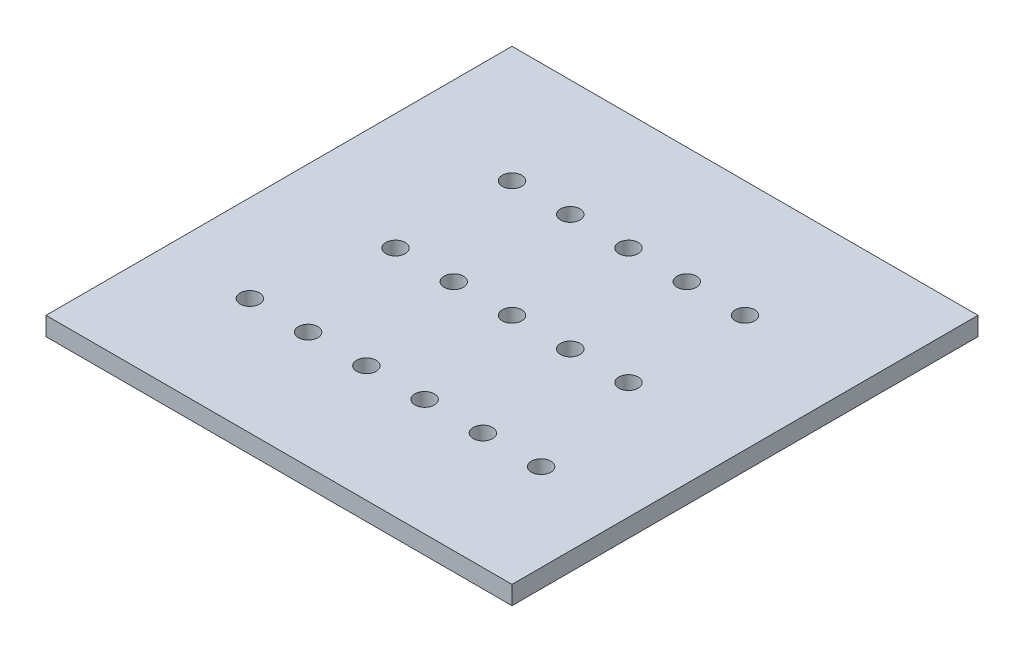
SolidWorks part; units mm, degrees
ref_plane "Front Plane" through (0, 0, 0) normal (0, 0, 1) x (1, 0, 0)
ref_plane "Top Plane" through (0, 0, 0) normal (0, 1, 0) x (1, 0, 0)
ref_plane "Right Plane" through (0, 0, 0) normal (1, 0, 0) x (0, 0, -1)
sketch "Sketch1" plane through (0, 0, 0) normal (0, 1, 0) x (1, 0, 0)
  line L0 (0, 90) -> (120, 90) construction
  line L1 (0, 0) -> (120, 0)
  line L2 (0, 0) -> (0, 120)
  line L3 (0, 120) -> (120, 120)
  line L4 (120, 0) -> (120, 120)
  line L5 (0, 30) -> (120, 30) construction
  line L6 (0, 60) -> (120, 60) construction
  line L7 (30, 90) -> (45, 90) construction
  line L8 (0, 75) -> (120, 75) construction
  line L9 (15.6387, 90) -> (15.6387, 75) construction
  line L10 (15.6387, 75) -> (15.6387, 60) construction
  line L11 (22.5, 30) -> (37.5, 30) construction
  circle A0 centre (30, 90) radius 2.5
  circle A1 centre (45, 90) radius 2.5
  circle A2 centre (60, 90) radius 2.5
  circle A3 centre (75, 90) radius 2.5
  circle A4 centre (90, 90) radius 2.5
  circle A5 centre (90, 60) radius 2.5
  circle A6 centre (75, 60) radius 2.5
  circle A7 centre (60, 60) radius 2.5
  circle A8 centre (45, 60) radius 2.5
  circle A9 centre (30, 60) radius 2.5
  circle A10 centre (22.5, 30) radius 2.5
  circle A11 centre (37.5, 30) radius 2.5
  circle A12 centre (52.5, 30) radius 2.5
  circle A13 centre (67.5, 30) radius 2.5
  circle A14 centre (82.5, 30) radius 2.5
  circle A15 centre (97.5, 30) radius 2.5
  dimension "D6" = 5
  dimension "D10" = 5
  dimension "D1" = 120
  dimension "D2" = 120
  dimension "D3" = 30
  dimension "D4" = 30
  dimension "D5" = 30
  dimension "D7" = 15
  dimension "D8" = 5
  dimension "D9" = 30
  dimension "D11" = 15
  dimension "D12" = 22.5
extrude "Boss-Extrude1" add sketch "Sketch1" along normal blind 4.7625
equation "\"LED_Diameter\"= 5"
